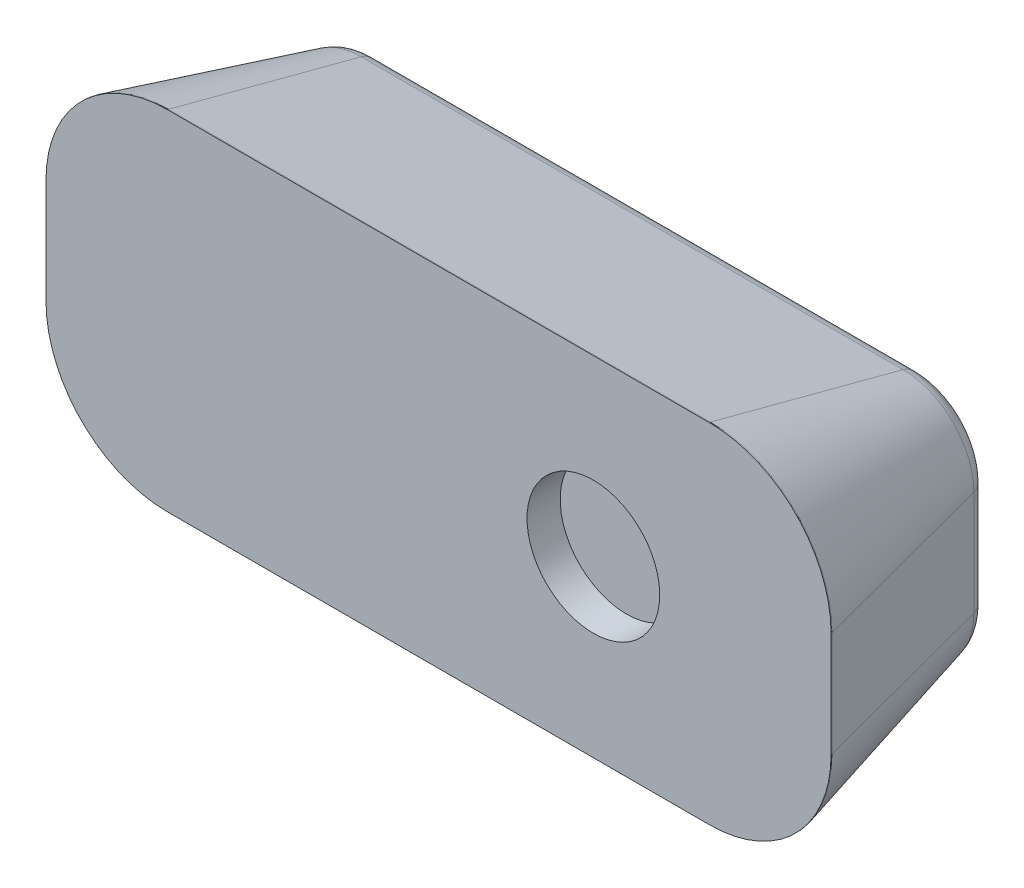
SolidWorks part; units mm, degrees
ref_plane "Front" through (0, 0, 0) normal (0, 0, 1) x (1, 0, 0)
ref_plane "Top" through (0, 0, 0) normal (0, 1, 0) x (1, 0, 0)
ref_plane "Right" through (0, 0, 0) normal (1, 0, 0) x (0, 0, -1)
sketch "Sketch1" plane through (0, 0, 0) normal (0, 0, 1) x (1, 0, 0)
  line L1 (35.5, -15.75) -> (-35.5, -15.75)
  line L2 (35.5, -15.75) -> (35.5, 15.75)
  line L3 (35.5, 15.75) -> (-35.5, 15.75)
  line L4 (-35.5, -15.75) -> (-35.5, 15.75)
  line L5 (35.5, -15.75) -> (-35.5, 15.75) construction
  line L6 (35.5, 15.75) -> (-35.5, -15.75) construction
  point P0 (0, 0)
  dimension "D1" = 71
  dimension "D2" = 31.5
extrude "Boss-Extrude1" add sketch "Sketch1" along normal mid plane 19
fillet "Fillet1" radius 11 4 edges at (-35.5, -15.75, 0) (-35.5, 15.75, 0) (35.5, -15.75, 0) (35.5, 15.75, 0)
chamfer "Chamfer1" distance 5 angle 75.2 8 edges at (0, -15.75, -9.5) (32.2782, -12.5282, -9.5) (-32.2782, -12.5282, -9.5) (35.5, 0, -9.5) (-35.5, 0, -9.5) (32.2782, 12.5282, -9.5) (-32.2782, 12.5282, -9.5) (0, 15.75, -9.5) first distance on face at (0, 0, -9.5)
sketch "Sketch2" plane through (0, 0, 0) normal (1, 0, 0) x (0, 0, -1)
  line L0 (9.5, 4.75) -> (9.5, -4.75) construction
  line L1 (15, -3.5) -> (9.5, -3.5)
  line L2 (15, -3.5) -> (15, 3.5)
  line L3 (15, 3.5) -> (9.5, 3.5)
  line L4 (9.5, -3.5) -> (9.5, 3.5)
  line L5 (15, -3.5) -> (9.5, 3.5) construction
  line L6 (15, 3.5) -> (9.5, -3.5) construction
  point P0 (12.25, 0)
  dimension "D1" = 5.5
  dimension "D2" = 7
extrude "Boss-Extrude2" add sketch "Sketch2" along normal blind 7
fillet "Fillet2" radius 3.5 2 edges at (3.5, -3.5, -15) (3.5, 3.5, -15)
sketch "Sketch3" plane through (7, 0, 0) normal (1, 0, 0) x (0, 0, -1)
  circle A0 centre (11.5, 0) radius 1.5
  dimension "D1" = 3
extrude "Cut-Extrude1" cut sketch "Sketch3" against normal up to surface (7 mm away) up to face at (0, 0, -11.6899)
fillet "Fillet3" radius 2 8 edges at (-28.7426, 8.9926, -9.5) (-30.5, 0, -9.5) (-28.7426, -8.9926, -9.5) (0, -10.75, -9.5) (28.7426, -8.9926, -9.5) (30.5, 0, -9.5) (28.7426, 8.9926, -9.5) (0, 10.75, -9.5)
sketch "Sketch4" plane through (0, 0, 9.5) normal (0, 0, 1) x (1, 0, 0)
  circle A0 centre (14, 0) radius 6
  dimension "D1" = 14
  dimension "D2" = 12
extrude "Cut-Extrude2" cut sketch "Sketch4" against normal blind 3
ref_axis "Axis1" through (14, 0, 6.5) along (0, 0, 1)
ref_plane "Plane1" through (14, 0, 0) normal (1, 0, 0) x (0, 0, -1)
sketch "Sketch5" plane through (14, 0, 0) normal (1, 0, 0) x (0, 0, -1)
  line L0 (-9.5, 0) -> (-129.5, 41.3193)
  line L1 (-129.5, 41.3193) -> (-129.5, -41.3193)
  line L2 (-129.5, -41.3193) -> (-9.5, 0)
  line L3 (-9.5, 0) -> (-129.5, 0) construction
  line L4 (-9.5, 6) -> (-9.5, -6) construction
  point P2 (0, 0)
  point P4 (0, 0)
  point P8 (-44.5965, -8.7558)
  point P9 (0, 0)
  point P11 (-79.2795, 0)
  dimension "D1" = 38
  dimension "D2" = 120
